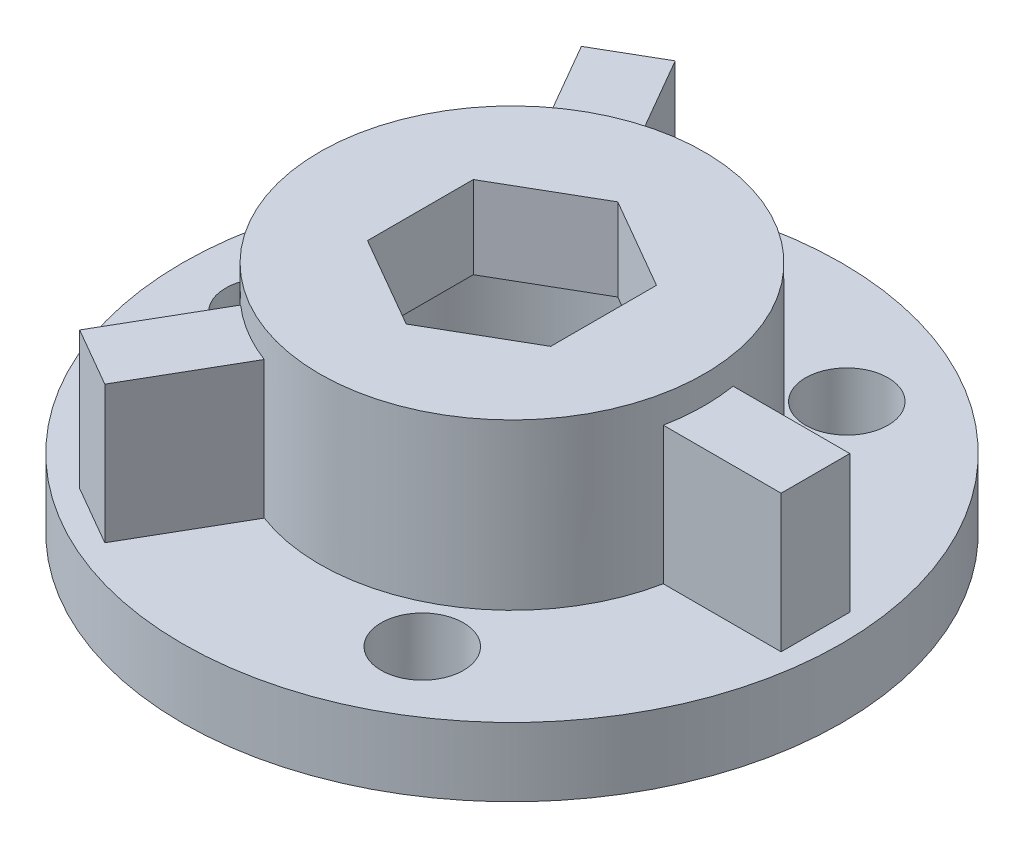
SolidWorks part; units mm, degrees
ref_plane "前视基准面" through (0, 0, 0) normal (0, 0, 1) x (1, 0, 0)
ref_plane "上视基准面" through (0, 0, 0) normal (0, 1, 0) x (1, 0, 0)
ref_plane "右视基准面" through (0, 0, 0) normal (1, 0, 0) x (0, 0, -1)
sketch "草图1" plane through (0, 0, 0) normal (0, 1, 0) x (1, 0, 0)
  circle A0 centre (0, 0) radius 12
extrude "凸台-拉伸1" add sketch "草图1" along normal blind 2.5
sketch "草图2" plane through (0, 2.5, 0) normal (0, 1, 0) x (1, 0, 0)
  circle A0 centre (0, 0) radius 5.7
extrude "切除-拉伸1" cut sketch "草图2" against normal blind 2.5
sketch "草图3" plane through (0, 2.5, 0) normal (0, 1, 0) x (1, 0, 0)
  circle A0 centre (0, 0) radius 7
extrude "凸台-拉伸2" add sketch "草图3" along normal blind 6
sketch "草图5" plane through (0, 8.5, 0) normal (0, 1, 0) x (1, 0, 0)
  line L0 (0, 0) -> (0, 6.5875) construction
  line L1 (3.3342, -1.925) -> (3.3342, 1.925)
  line L2 (0, 3.85) -> (3.3342, 1.925)
  line L3 (-3.3342, 1.925) -> (0, 3.85)
  line L19 (-3.3342, 1.925) -> (-3.3342, -1.925)
  line L21 (-3.3342, -1.925) -> (0, -3.85)
  line L22 (0, -3.85) -> (3.3342, -1.925)
  point P31 (0, 0)
extrude "切除-拉伸3" cut sketch "草图5" against normal through all
sketch "草图6" plane through (0, 2.5, 0) normal (0, -1, 0) x (1, 0, 0)
  circle A0 centre (0, 0) radius 5.7
extrude "切除-拉伸4" cut sketch "草图6" against normal blind 3
ref_axis "基准轴1" through (0, 8.5, 0) along (0, -1, 0)
sketch "草图12" plane through (0, 0, 0) normal (0, -1, 0) x (-1, 0, 0)
  line L0 (0, 0) -> (0, 10.3288) construction
  line L1 (0, 0) -> (-5.1772, 8.9672) construction
  circle A1 centre (-4.46, 7.7249) radius 1.5
  dimension "D1" = 30
  dimension "D2" = 3
  dimension "D3" = 8.92
extrude "切除-拉伸7" cut sketch "草图12" against normal blind 8.5
pattern_circular "阵列(圆周)3" count 3 over 360 about axis through (0, 8.5, 0) along (0, -1, 0) of "切除-拉伸7"
sketch "草图16" plane through (0, 2.5, 0) normal (0, 1, 0) x (1, 0, 0)
  line L1 (11.1547, 1.1398) -> (6.3136, 1.1398)
  line L2 (11.1547, 1.1398) -> (11.1547, -1.3602)
  line L3 (11.1547, -1.3602) -> (6.3136, -1.3602)
  line L4 (6.3136, 1.1398) -> (6.3136, -1.3602)
  line L5 (11.1547, 1.1398) -> (6.3136, -1.3602) construction
  line L6 (11.1547, -1.3602) -> (6.3136, 1.1398) construction
  point P0 (8.7341, -0.1102)
extrude "凸台-拉伸5" add sketch "草图16" along normal blind 5
pattern_circular "阵列(圆周)4" count 3 over 360 about axis through (0, 8.5, 0) along (0, -1, 0) of "凸台-拉伸5"
